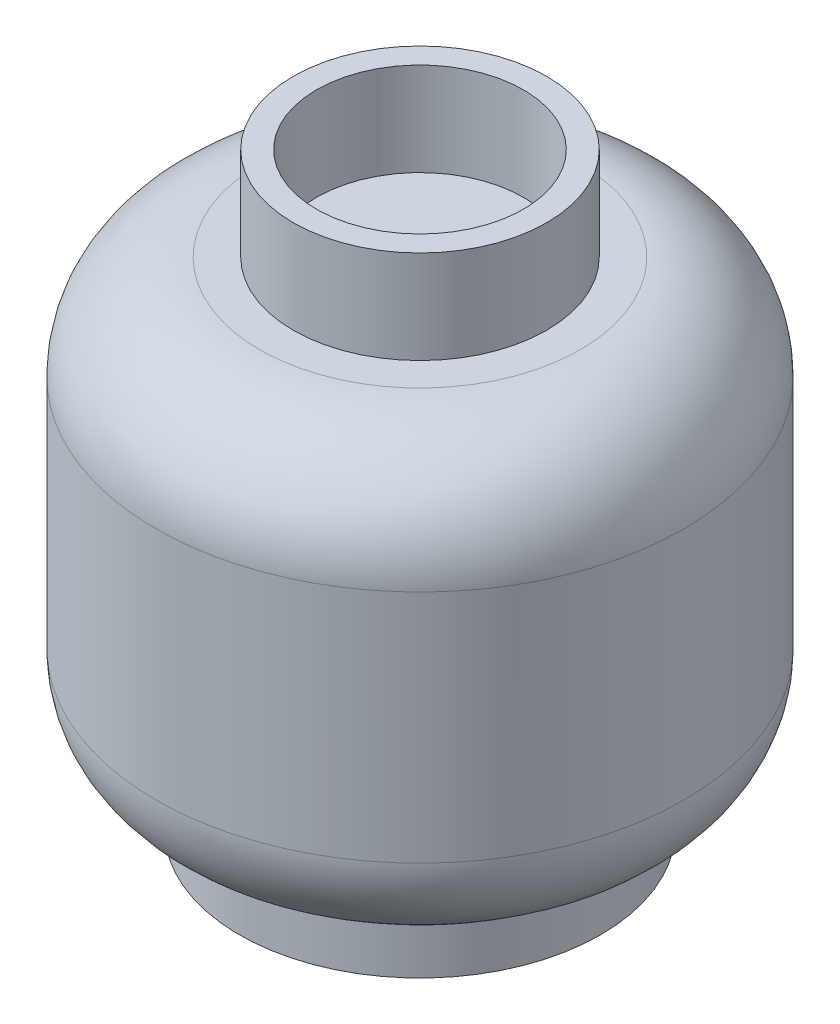
SolidWorks part; units mm, degrees
ref_plane "Front Plane" through (0, 0, 0) normal (0, 0, 1) x (1, 0, 0)
ref_plane "Top Plane" through (0, 0, 0) normal (0, 1, 0) x (1, 0, 0)
ref_plane "Right Plane" through (0, 0, 0) normal (1, 0, 0) x (0, 0, -1)
sketch "Sketch2" plane through (0, 0, 0) normal (0, 0, 1) x (1, 0, 0)
  line L0 (0, -5.7) -> (0, 5.7)
  line L1 (0, 5.7) -> (2.45, 5.7)
  line L2 (2.45, 5.7) -> (2.45, 3.9)
  line L3 (2.45, 3.9) -> (5.1, 3.9)
  line L4 (5.1, 3.9) -> (5.1, -4.6)
  line L5 (5.1, -4.6) -> (3.489, -4.6)
  line L6 (3.489, -4.6) -> (3.489, -5.7)
  line L7 (3.489, -5.7) -> (0, -5.7)
  point P4 (0, 0)
  dimension "D1" = 2.45
  dimension "D2" = 9.6
  dimension "D3" = 1.8
  dimension "D5" = 8.5
  dimension "D6" = 5.1
revolve "Revolve2" add sketch "Sketch2" angle 360 about L0
fillet "Fillet1" radius 2 2 edges at (5.1, -4.6, 0) (5.1, 3.9, 0)
sketch "Sketch3" plane through (0, -5.7, 0) normal (0, -1, 0) x (1, 0, 0)
  circle A0 centre (0, 0) radius 2.5
  dimension "D1" = 5
extrude "Cut-Extrude1" cut sketch "Sketch3" against normal blind 6
sketch "Sketch4" plane through (0, 5.7, 0) normal (0, 1, 0) x (1, 0, 0)
  circle A0 centre (0, 0) radius 2
  dimension "D1" = 4
extrude "Cut-Extrude2" cut sketch "Sketch4" against normal blind 1.8
